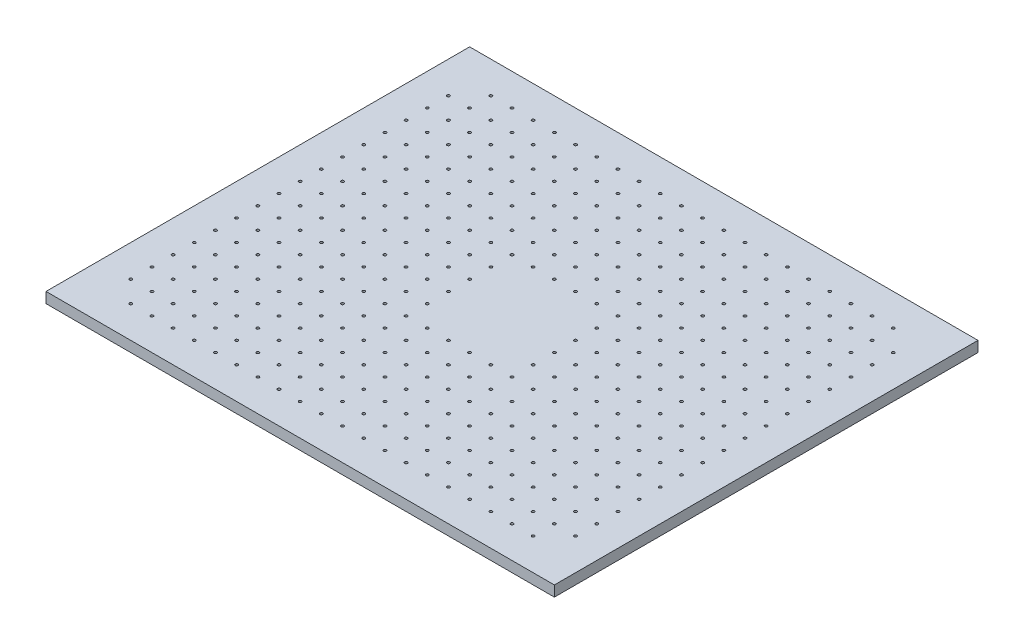
SolidWorks part; units mm, degrees
ref_plane "Alzado" through (0, 0, 0) normal (0, 0, 1) x (1, 0, 0)
ref_plane "Planta" through (0, 0, 0) normal (0, 1, 0) x (1, 0, 0)
ref_plane "Vista lateral" through (0, 0, 0) normal (1, 0, 0) x (0, 0, -1)
sketch "Croquis_tablero" plane through (0, 0, 0) normal (0, 1, 0) x (1, 0, 0)
  line L1 (-600, -500) -> (600, -500)
  line L2 (-600, -500) -> (-600, 500)
  line L3 (-600, 500) -> (600, 500)
  line L4 (600, -500) -> (600, 500)
  line L5 (-600, -500) -> (600, 500) construction
  line L6 (-600, 500) -> (600, -500) construction
  point P0 (0, 0)
  dimension "D1" = 600
  dimension "D2" = 500
extrude "Tablero_1200x1000x25" add sketch "Croquis_tablero" against normal blind 25
sketch "Croquis_rejilla_M6_paso50" plane through (0, 0, 0) normal (0, 1, 0) x (1, 0, 0)
  circle A0 centre (-525, -375) radius 3.3
  circle A1 centre (-525, -325) radius 3.3
  circle A2 centre (-525, -275) radius 3.3
  circle A3 centre (-525, -225) radius 3.3
  circle A4 centre (-525, -175) radius 3.3
  circle A5 centre (-525, -125) radius 3.3
  circle A6 centre (-525, -75) radius 3.3
  circle A7 centre (-525, -25) radius 3.3
  circle A8 centre (-525, 25) radius 3.3
  circle A9 centre (-525, 75) radius 3.3
  circle A10 centre (-525, 125) radius 3.3
  circle A11 centre (-525, 175) radius 3.3
  circle A12 centre (-525, 225) radius 3.3
  circle A13 centre (-525, 275) radius 3.3
  circle A14 centre (-525, 325) radius 3.3
  circle A15 centre (-525, 375) radius 3.3
  circle A16 centre (-475, -425) radius 3.3
  circle A17 centre (-475, -375) radius 3.3
  circle A18 centre (-475, -325) radius 3.3
  circle A19 centre (-475, -275) radius 3.3
  circle A20 centre (-475, -225) radius 3.3
  circle A21 centre (-475, -175) radius 3.3
  circle A22 centre (-475, -125) radius 3.3
  circle A23 centre (-475, -75) radius 3.3
  circle A24 centre (-475, -25) radius 3.3
  circle A25 centre (-475, 25) radius 3.3
  circle A26 centre (-475, 75) radius 3.3
  circle A27 centre (-475, 125) radius 3.3
  circle A28 centre (-475, 175) radius 3.3
  circle A29 centre (-475, 225) radius 3.3
  circle A30 centre (-475, 275) radius 3.3
  circle A31 centre (-475, 325) radius 3.3
  circle A32 centre (-475, 375) radius 3.3
  circle A33 centre (-475, 425) radius 3.3
  circle A34 centre (-425, -425) radius 3.3
  circle A35 centre (-425, -375) radius 3.3
  circle A36 centre (-425, -325) radius 3.3
  circle A37 centre (-425, -275) radius 3.3
  circle A38 centre (-425, -225) radius 3.3
  circle A39 centre (-425, -175) radius 3.3
  circle A40 centre (-425, -125) radius 3.3
  circle A41 centre (-425, -75) radius 3.3
  circle A42 centre (-425, -25) radius 3.3
  circle A43 centre (-425, 25) radius 3.3
  circle A44 centre (-425, 75) radius 3.3
  circle A45 centre (-425, 125) radius 3.3
  circle A46 centre (-425, 175) radius 3.3
  circle A47 centre (-425, 225) radius 3.3
  circle A48 centre (-425, 275) radius 3.3
  circle A49 centre (-425, 325) radius 3.3
  circle A50 centre (-425, 375) radius 3.3
  circle A51 centre (-425, 425) radius 3.3
  circle A52 centre (-375, -425) radius 3.3
  circle A53 centre (-375, -375) radius 3.3
  circle A54 centre (-375, -325) radius 3.3
  circle A55 centre (-375, -275) radius 3.3
  circle A56 centre (-375, -225) radius 3.3
  circle A57 centre (-375, -175) radius 3.3
  circle A58 centre (-375, -125) radius 3.3
  circle A59 centre (-375, -75) radius 3.3
  circle A60 centre (-375, -25) radius 3.3
  circle A61 centre (-375, 25) radius 3.3
  circle A62 centre (-375, 75) radius 3.3
  circle A63 centre (-375, 125) radius 3.3
  circle A64 centre (-375, 175) radius 3.3
  circle A65 centre (-375, 225) radius 3.3
  circle A66 centre (-375, 275) radius 3.3
  circle A67 centre (-375, 325) radius 3.3
  circle A68 centre (-375, 375) radius 3.3
  circle A69 centre (-375, 425) radius 3.3
  circle A70 centre (-325, -425) radius 3.3
  circle A71 centre (-325, -375) radius 3.3
  circle A72 centre (-325, -325) radius 3.3
  circle A73 centre (-325, -275) radius 3.3
  circle A74 centre (-325, -225) radius 3.3
  circle A75 centre (-325, -175) radius 3.3
  circle A76 centre (-325, -125) radius 3.3
  circle A77 centre (-325, -75) radius 3.3
  circle A78 centre (-325, -25) radius 3.3
  circle A79 centre (-325, 25) radius 3.3
  circle A80 centre (-325, 75) radius 3.3
  circle A81 centre (-325, 125) radius 3.3
  circle A82 centre (-325, 175) radius 3.3
  circle A83 centre (-325, 225) radius 3.3
  circle A84 centre (-325, 275) radius 3.3
  circle A85 centre (-325, 325) radius 3.3
  circle A86 centre (-325, 375) radius 3.3
  circle A87 centre (-325, 425) radius 3.3
  circle A88 centre (-275, -425) radius 3.3
  circle A89 centre (-275, -375) radius 3.3
  circle A90 centre (-275, -325) radius 3.3
  circle A91 centre (-275, -275) radius 3.3
  circle A92 centre (-275, -225) radius 3.3
  circle A93 centre (-275, -175) radius 3.3
  circle A94 centre (-275, -125) radius 3.3
  circle A95 centre (-275, -75) radius 3.3
  circle A96 centre (-275, -25) radius 3.3
  circle A97 centre (-275, 25) radius 3.3
  circle A98 centre (-275, 75) radius 3.3
  circle A99 centre (-275, 125) radius 3.3
  circle A100 centre (-275, 175) radius 3.3
  circle A101 centre (-275, 225) radius 3.3
  circle A102 centre (-275, 275) radius 3.3
  circle A103 centre (-275, 325) radius 3.3
  circle A104 centre (-275, 375) radius 3.3
  circle A105 centre (-275, 425) radius 3.3
  circle A106 centre (-225, -425) radius 3.3
  circle A107 centre (-225, -375) radius 3.3
  circle A108 centre (-225, -325) radius 3.3
  circle A109 centre (-225, -275) radius 3.3
  circle A110 centre (-225, -225) radius 3.3
  circle A111 centre (-225, -175) radius 3.3
  circle A112 centre (-225, -125) radius 3.3
  circle A113 centre (-225, -75) radius 3.3
  circle A114 centre (-225, -25) radius 3.3
  circle A115 centre (-225, 25) radius 3.3
  circle A116 centre (-225, 75) radius 3.3
  circle A117 centre (-225, 125) radius 3.3
  circle A118 centre (-225, 175) radius 3.3
  circle A119 centre (-225, 225) radius 3.3
  circle A120 centre (-225, 275) radius 3.3
  circle A121 centre (-225, 325) radius 3.3
  circle A122 centre (-225, 375) radius 3.3
  circle A123 centre (-225, 425) radius 3.3
  circle A124 centre (-175, -425) radius 3.3
  circle A125 centre (-175, -375) radius 3.3
  circle A126 centre (-175, -325) radius 3.3
  circle A127 centre (-175, -275) radius 3.3
  circle A128 centre (-175, -225) radius 3.3
  circle A129 centre (-175, -175) radius 3.3
  circle A130 centre (-175, -125) radius 3.3
  circle A131 centre (-175, -75) radius 3.3
  circle A132 centre (-175, -25) radius 3.3
  circle A133 centre (-175, 25) radius 3.3
  circle A134 centre (-175, 75) radius 3.3
  circle A135 centre (-175, 125) radius 3.3
  circle A136 centre (-175, 175) radius 3.3
  circle A137 centre (-175, 225) radius 3.3
  circle A138 centre (-175, 275) radius 3.3
  circle A139 centre (-175, 325) radius 3.3
  circle A140 centre (-175, 375) radius 3.3
  circle A141 centre (-175, 425) radius 3.3
  circle A142 centre (-125, -425) radius 3.3
  circle A143 centre (-125, -375) radius 3.3
  circle A144 centre (-125, -325) radius 3.3
  circle A145 centre (-125, -275) radius 3.3
  circle A146 centre (-125, -225) radius 3.3
  circle A147 centre (-125, -175) radius 3.3
  circle A148 centre (-125, -125) radius 3.3
  circle A149 centre (-125, -75) radius 3.3
  circle A150 centre (-125, -25) radius 3.3
  circle A151 centre (-125, 25) radius 3.3
  circle A152 centre (-125, 75) radius 3.3
  circle A153 centre (-125, 125) radius 3.3
  circle A154 centre (-125, 175) radius 3.3
  circle A155 centre (-125, 225) radius 3.3
  circle A156 centre (-125, 275) radius 3.3
  circle A157 centre (-125, 325) radius 3.3
  circle A158 centre (-125, 375) radius 3.3
  circle A159 centre (-125, 425) radius 3.3
  circle A160 centre (-75, -425) radius 3.3
  circle A161 centre (-75, -375) radius 3.3
  circle A162 centre (-75, -325) radius 3.3
  circle A163 centre (-75, -275) radius 3.3
  circle A164 centre (-75, -225) radius 3.3
  circle A165 centre (-75, -175) radius 3.3
  circle A166 centre (-75, -125) radius 3.3
  circle A167 centre (-75, 125) radius 3.3
  circle A168 centre (-75, 175) radius 3.3
  circle A169 centre (-75, 225) radius 3.3
  circle A170 centre (-75, 275) radius 3.3
  circle A171 centre (-75, 325) radius 3.3
  circle A172 centre (-75, 375) radius 3.3
  circle A173 centre (-75, 425) radius 3.3
  circle A174 centre (-25, -425) radius 3.3
  circle A175 centre (-25, -375) radius 3.3
  circle A176 centre (-25, -325) radius 3.3
  circle A177 centre (-25, -275) radius 3.3
  circle A178 centre (-25, -225) radius 3.3
  circle A179 centre (-25, -175) radius 3.3
  circle A180 centre (-25, -125) radius 3.3
  circle A181 centre (-25, 125) radius 3.3
  circle A182 centre (-25, 175) radius 3.3
  circle A183 centre (-25, 225) radius 3.3
  circle A184 centre (-25, 275) radius 3.3
  circle A185 centre (-25, 325) radius 3.3
  circle A186 centre (-25, 375) radius 3.3
  circle A187 centre (-25, 425) radius 3.3
  circle A188 centre (25, -425) radius 3.3
  circle A189 centre (25, -375) radius 3.3
  circle A190 centre (25, -325) radius 3.3
  circle A191 centre (25, -275) radius 3.3
  circle A192 centre (25, -225) radius 3.3
  circle A193 centre (25, -175) radius 3.3
  circle A194 centre (25, -125) radius 3.3
  circle A195 centre (25, 125) radius 3.3
  circle A196 centre (25, 175) radius 3.3
  circle A197 centre (25, 225) radius 3.3
  circle A198 centre (25, 275) radius 3.3
  circle A199 centre (25, 325) radius 3.3
  circle A200 centre (25, 375) radius 3.3
  circle A201 centre (25, 425) radius 3.3
  circle A202 centre (75, -425) radius 3.3
  circle A203 centre (75, -375) radius 3.3
  circle A204 centre (75, -325) radius 3.3
  circle A205 centre (75, -275) radius 3.3
  circle A206 centre (75, -225) radius 3.3
  circle A207 centre (75, -175) radius 3.3
  circle A208 centre (75, -125) radius 3.3
  circle A209 centre (75, 125) radius 3.3
  circle A210 centre (75, 175) radius 3.3
  circle A211 centre (75, 225) radius 3.3
  circle A212 centre (75, 275) radius 3.3
  circle A213 centre (75, 325) radius 3.3
  circle A214 centre (75, 375) radius 3.3
  circle A215 centre (75, 425) radius 3.3
  circle A216 centre (125, -425) radius 3.3
  circle A217 centre (125, -375) radius 3.3
  circle A218 centre (125, -325) radius 3.3
  circle A219 centre (125, -275) radius 3.3
  circle A220 centre (125, -225) radius 3.3
  circle A221 centre (125, -175) radius 3.3
  circle A222 centre (125, -125) radius 3.3
  circle A223 centre (125, -75) radius 3.3
  circle A224 centre (125, -25) radius 3.3
  circle A225 centre (125, 25) radius 3.3
  circle A226 centre (125, 75) radius 3.3
  circle A227 centre (125, 125) radius 3.3
  circle A228 centre (125, 175) radius 3.3
  circle A229 centre (125, 225) radius 3.3
  circle A230 centre (125, 275) radius 3.3
  circle A231 centre (125, 325) radius 3.3
  circle A232 centre (125, 375) radius 3.3
  circle A233 centre (125, 425) radius 3.3
  circle A234 centre (175, -425) radius 3.3
  circle A235 centre (175, -375) radius 3.3
  circle A236 centre (175, -325) radius 3.3
  circle A237 centre (175, -275) radius 3.3
  circle A238 centre (175, -225) radius 3.3
  circle A239 centre (175, -175) radius 3.3
  circle A240 centre (175, -125) radius 3.3
  circle A241 centre (175, -75) radius 3.3
  circle A242 centre (175, -25) radius 3.3
  circle A243 centre (175, 25) radius 3.3
  circle A244 centre (175, 75) radius 3.3
  circle A245 centre (175, 125) radius 3.3
  circle A246 centre (175, 175) radius 3.3
  circle A247 centre (175, 225) radius 3.3
  circle A248 centre (175, 275) radius 3.3
  circle A249 centre (175, 325) radius 3.3
  circle A250 centre (175, 375) radius 3.3
  circle A251 centre (175, 425) radius 3.3
  circle A252 centre (225, -425) radius 3.3
  circle A253 centre (225, -375) radius 3.3
  circle A254 centre (225, -325) radius 3.3
  circle A255 centre (225, -275) radius 3.3
  circle A256 centre (225, -225) radius 3.3
  circle A257 centre (225, -175) radius 3.3
  circle A258 centre (225, -125) radius 3.3
  circle A259 centre (225, -75) radius 3.3
  circle A260 centre (225, -25) radius 3.3
  circle A261 centre (225, 25) radius 3.3
  circle A262 centre (225, 75) radius 3.3
  circle A263 centre (225, 125) radius 3.3
  circle A264 centre (225, 175) radius 3.3
  circle A265 centre (225, 225) radius 3.3
  circle A266 centre (225, 275) radius 3.3
  circle A267 centre (225, 325) radius 3.3
  circle A268 centre (225, 375) radius 3.3
  circle A269 centre (225, 425) radius 3.3
  circle A270 centre (275, -425) radius 3.3
  circle A271 centre (275, -375) radius 3.3
  circle A272 centre (275, -325) radius 3.3
  circle A273 centre (275, -275) radius 3.3
  circle A274 centre (275, -225) radius 3.3
  circle A275 centre (275, -175) radius 3.3
  circle A276 centre (275, -125) radius 3.3
  circle A277 centre (275, -75) radius 3.3
  circle A278 centre (275, -25) radius 3.3
  circle A279 centre (275, 25) radius 3.3
  circle A280 centre (275, 75) radius 3.3
  circle A281 centre (275, 125) radius 3.3
  circle A282 centre (275, 175) radius 3.3
  circle A283 centre (275, 225) radius 3.3
  circle A284 centre (275, 275) radius 3.3
  circle A285 centre (275, 325) radius 3.3
  circle A286 centre (275, 375) radius 3.3
  circle A287 centre (275, 425) radius 3.3
  circle A288 centre (325, -425) radius 3.3
  circle A289 centre (325, -375) radius 3.3
  circle A290 centre (325, -325) radius 3.3
  circle A291 centre (325, -275) radius 3.3
  circle A292 centre (325, -225) radius 3.3
  circle A293 centre (325, -175) radius 3.3
  circle A294 centre (325, -125) radius 3.3
  circle A295 centre (325, -75) radius 3.3
  circle A296 centre (325, -25) radius 3.3
  circle A297 centre (325, 25) radius 3.3
  circle A298 centre (325, 75) radius 3.3
  circle A299 centre (325, 125) radius 3.3
  circle A300 centre (325, 175) radius 3.3
  circle A301 centre (325, 225) radius 3.3
  circle A302 centre (325, 275) radius 3.3
  circle A303 centre (325, 325) radius 3.3
  circle A304 centre (325, 375) radius 3.3
  circle A305 centre (325, 425) radius 3.3
  circle A306 centre (375, -425) radius 3.3
  circle A307 centre (375, -375) radius 3.3
  circle A308 centre (375, -325) radius 3.3
  circle A309 centre (375, -275) radius 3.3
  circle A310 centre (375, -225) radius 3.3
  circle A311 centre (375, -175) radius 3.3
  circle A312 centre (375, -125) radius 3.3
  circle A313 centre (375, -75) radius 3.3
  circle A314 centre (375, -25) radius 3.3
  circle A315 centre (375, 25) radius 3.3
  circle A316 centre (375, 75) radius 3.3
  circle A317 centre (375, 125) radius 3.3
  circle A318 centre (375, 175) radius 3.3
  circle A319 centre (375, 225) radius 3.3
  circle A320 centre (375, 275) radius 3.3
  circle A321 centre (375, 325) radius 3.3
  circle A322 centre (375, 375) radius 3.3
  circle A323 centre (375, 425) radius 3.3
  circle A324 centre (425, -425) radius 3.3
  circle A325 centre (425, -375) radius 3.3
  circle A326 centre (425, -325) radius 3.3
  circle A327 centre (425, -275) radius 3.3
  circle A328 centre (425, -225) radius 3.3
  circle A329 centre (425, -175) radius 3.3
  circle A330 centre (425, -125) radius 3.3
  circle A331 centre (425, -75) radius 3.3
  circle A332 centre (425, -25) radius 3.3
  circle A333 centre (425, 25) radius 3.3
  circle A334 centre (425, 75) radius 3.3
  circle A335 centre (425, 125) radius 3.3
  circle A336 centre (425, 175) radius 3.3
  circle A337 centre (425, 225) radius 3.3
  circle A338 centre (425, 275) radius 3.3
  circle A339 centre (425, 325) radius 3.3
  circle A340 centre (425, 375) radius 3.3
  circle A341 centre (425, 425) radius 3.3
  circle A342 centre (475, -425) radius 3.3
  circle A343 centre (475, -375) radius 3.3
  circle A344 centre (475, -325) radius 3.3
  circle A345 centre (475, -275) radius 3.3
  circle A346 centre (475, -225) radius 3.3
  circle A347 centre (475, -175) radius 3.3
  circle A348 centre (475, -125) radius 3.3
  circle A349 centre (475, -75) radius 3.3
  circle A350 centre (475, -25) radius 3.3
  circle A351 centre (475, 25) radius 3.3
  circle A352 centre (475, 75) radius 3.3
  circle A353 centre (475, 125) radius 3.3
  circle A354 centre (475, 175) radius 3.3
  circle A355 centre (475, 225) radius 3.3
  circle A356 centre (475, 275) radius 3.3
  circle A357 centre (475, 325) radius 3.3
  circle A358 centre (475, 375) radius 3.3
  circle A359 centre (475, 425) radius 3.3
  circle A360 centre (525, -375) radius 3.3
  circle A361 centre (525, -325) radius 3.3
  circle A362 centre (525, -275) radius 3.3
  circle A363 centre (525, -225) radius 3.3
  circle A364 centre (525, -175) radius 3.3
  circle A365 centre (525, -125) radius 3.3
  circle A366 centre (525, -75) radius 3.3
  circle A367 centre (525, -25) radius 3.3
  circle A368 centre (525, 25) radius 3.3
  circle A369 centre (525, 75) radius 3.3
  circle A370 centre (525, 125) radius 3.3
  circle A371 centre (525, 175) radius 3.3
  circle A372 centre (525, 225) radius 3.3
  circle A373 centre (525, 275) radius 3.3
  circle A374 centre (525, 325) radius 3.3
  circle A375 centre (525, 375) radius 3.3
extrude "Rejilla_agujeros_M6_D6.6" cut sketch "Croquis_rejilla_M6_paso50" against normal through all and the other way through all
